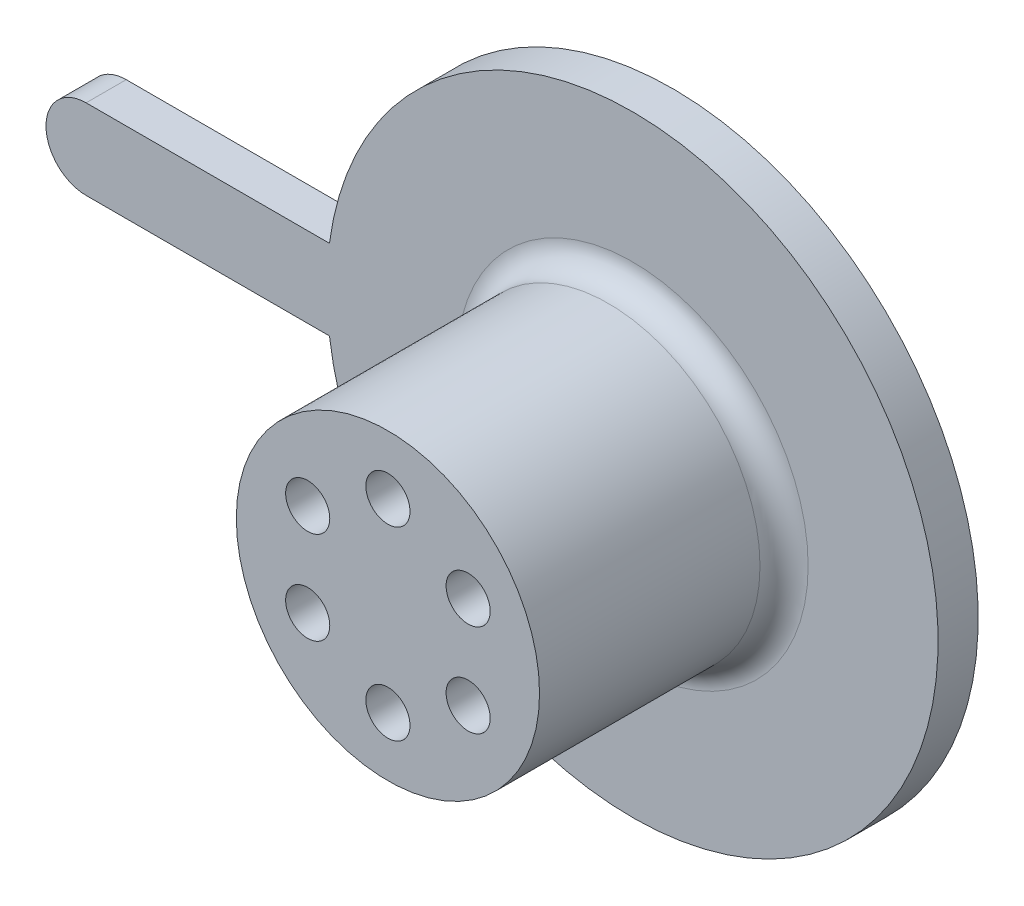
SolidWorks part; units mm, degrees
ref_plane "Front Plane" through (0, 0, 0) normal (0, 0, 1) x (1, 0, 0)
ref_plane "Top Plane" through (0, 0, 0) normal (0, 1, 0) x (1, 0, 0)
ref_plane "Right Plane" through (0, 0, 0) normal (1, 0, 0) x (0, 0, -1)
sketch "Sketch4" plane through (0, 0, 0) normal (0, 0, 1) x (1, 0, 0)
  line L0 (-38.1, 0) -> (-68.1, 0)
  line L1 (-68.1, 0) -> (-68.1, 5)
  line L2 (-68.1, 0) -> (-68.1, -5)
  line L3 (-68.1, 5) -> (-37.7705, 5)
  line L4 (-68.1, -5) -> (-37.7705, -5)
  circle A0 centre (0, 0) radius 38.1
  arc A1 (-68.1, 5) -> (-68.1, -5) centre (-68.1, 0) ccw
  dimension "D1" = 30
  dimension "D2" = 76.2
extrude "Boss-Extrude3" add sketch "Sketch4" along normal blind 5 contours A0 | A0 L3 L1 L0 | A0 L0 L2 L4 | L1 A1 L2 region at (-53.045, -2.5046, 0) region at (-53.045, 2.5046, 0) region at (0, 0, 0) region at (-70.2221, 0, 0)
sketch "Sketch5" plane through (0, 0, 5) normal (0, 0, 1) x (1, 0, 0)
  circle A0 centre (0, 0) radius 18.9
extrude "Boss-Extrude4" add sketch "Sketch5" along normal blind 30.48
fillet "Fillet4" radius 3 1 edges at (18.9, 0, 5)
sketch "Sketch6" plane through (0, 0, 35.48) normal (0, 0, 1) x (1, 0, 0)
  line L1 (0, 11.547) -> (-10, 5.7735)
  line L2 (-10, 5.7735) -> (-10, -5.7735)
  line L3 (-10, -5.7735) -> (0, -11.547)
  line L4 (0, -11.547) -> (10, -5.7735)
  line L5 (10, -5.7735) -> (10, 5.7735)
  line L6 (10, 5.7735) -> (0, 11.547)
  circle A0 centre (0, 0) radius 10 construction
  circle A1 centre (0, 11.547) radius 2.75
  circle A2 centre (10, 5.7735) radius 2.75
  circle A3 centre (10, -5.7735) radius 2.75
  circle A4 centre (0, -11.547) radius 2.75
  circle A5 centre (-10, -5.7735) radius 2.75
  circle A6 centre (-10, 5.7735) radius 2.75
extrude "Cut-Extrude4" cut sketch "Sketch6" against normal blind 39.48 contours L6 A1 L1 | L1 A1 L6 | L5 A2 L6 | L6 A2 L5 | L4 A3 L5 | L5 A3 L4 | L1 A6 L2 | L2 A6 L1 | L3 A5 L2 | L2 A5 L3 | L3 A4 L4 | L4 A4 L3 region at (0, 10.0309, 35.48) region at (0, 12.3051, 35.48) region at (-8.687, 5.0154, 35.48) region at (-10.6565, 6.1525, 35.48) region at (10.6565, 6.1525, 35.48) region at (8.687, 5.0154, 35.48) region at (-8.687, -5.0154, 35.48) region at (-10.6565, -6.1525, 35.48) region at (10.6565, -6.1525, 35.48) region at (8.687, -5.0154, 35.48) region at (0, -10.0309, 35.48) region at (0, -12.3051, 35.48)
